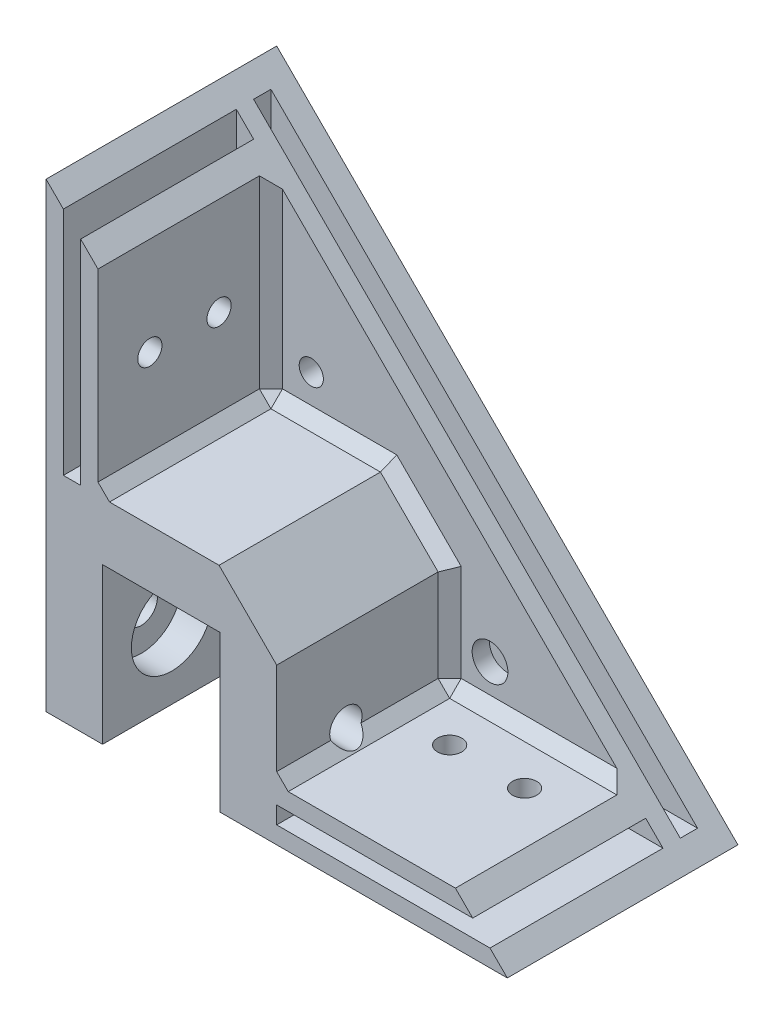
SolidWorks part; units mm, degrees
material "ABS"
ref_plane "Płaszczyzna przednia" through (0, 0, 0) normal (0, 0, 1) x (1, 0, 0)
ref_plane "Płaszczyzna górna" through (0, 0, 0) normal (0, 1, 0) x (1, 0, 0)
ref_plane "Płaszczyzna prawa" through (0, 0, 0) normal (1, 0, 0) x (0, 0, -1)
sketch "Szkic1" plane through (0, 0, 0) normal (0, 0, 1) x (1, 0, 0)
  line L0 (0, 0) -> (80, 0)
  line L1 (0, 0) -> (0, 80)
  line L2 (0, 80) -> (80, 0)
  dimension "D1" = 80
  dimension "D2" = 80
extrude "Dodanie-wyciągnięcie1" add sketch "Szkic1" along normal blind 4
sketch "Szkic2" plane through (0, 0, 4) normal (0, 0, 1) x (1, 0, 0)
  line L0 (3, 77) -> (3, 3)
  line L1 (80, 0) -> (0, 80) construction
  line L2 (3, 3) -> (77, 3)
  line L3 (0, 0) -> (80, 0) construction
  line L4 (0, 80) -> (0, 0) construction
  line L5 (0, 0) -> (80, 0)
  line L6 (0, 80) -> (0, 0)
  line L7 (80, 0) -> (77, 3)
  line L8 (3, 77) -> (0, 80)
  dimension "D1" = 3
  dimension "D2" = 3
extrude "Dodanie-wyciągnięcie2" add sketch "Szkic2" along normal blind 3
sketch "Szkic3" plane through (0, 0, 7) normal (0, 0, 1) x (1, 0, 0)
  line L0 (80, 0) -> (77, 3) construction
  line L1 (0, 0) -> (80, 0) construction
  line L2 (0, 80) -> (0, 0) construction
  line L3 (3, 77) -> (0, 80) construction
  line L4 (77, 3) -> (3, 77) construction
  line L5 (80, 0) -> (77, 3)
  line L6 (0, 0) -> (80, 0)
  line L7 (0, 80) -> (0, 0)
  line L8 (3, 77) -> (0, 80)
  line L9 (77, 3) -> (3, 77)
extrude "Dodanie-wyciągnięcie3" add sketch "Szkic3" along normal blind 3
sketch "Szkic4" plane through (0, 0, 10) normal (0, 0, 1) x (1, 0, 0)
  line L0 (80, 0) -> (30.2, 0)
  line L1 (0, 0) -> (80, 0) construction
  line L2 (77, 3) -> (40, 3)
  line L3 (80, 0) -> (0, 80) construction
  line L4 (40, 3) -> (40, 6)
  line L5 (40, 6) -> (74, 6)
  line L6 (71, 9) -> (40, 9)
  line L7 (0, 0) -> (9.8, 0)
  line L8 (9.8, 0) -> (9.8, 27)
  line L9 (9.8, 27) -> (30.2, 27)
  line L10 (30.2, 27) -> (30.2, 0)
  line L11 (0, 80) -> (0, 0)
  line L12 (40, 9) -> (40, 27)
  line L13 (3, 77) -> (3, 37)
  line L14 (3, 37) -> (6, 37)
  line L15 (6, 37) -> (6, 74)
  line L16 (9, 71) -> (9, 37)
  line L17 (9, 37) -> (30, 37)
  line L18 (30, 37) -> (40, 27)
  line M3 (0, 0) -> (80, 0)
  line M4 (80, 0) -> (0, 80)
  line M5 (0, 80) -> (0, 0)
  dimension "D1" = 49.8
  dimension "D2" = 3
  dimension "D3" = 37
  dimension "D4" = 3
  dimension "D5" = 3
  dimension "D6" = 9.8
  dimension "D7" = 27
  dimension "D8" = 27
  dimension "D9" = 3
  dimension "D10" = 43
  dimension "D11" = 3
  dimension "D12" = 3
  dimension "D13" = 21
extrude "Dodanie-wyciągnięcie4" add sketch "Szkic4" along normal blind 30 contours L18 L17 L16 L15 L14 L13 L8 L9 L10 L2 L4 L5 L6 L12 M4 M5 M3 region at (55.1, 1.1314, 10)
ref_plane "Płaszczyzna1" through (20, 0, 0) normal (1, 0, 0) x (0, 0, -1)
sketch "Szkic5" plane through (20, 0, 0) normal (1, 0, 0) x (0, 0, -1)
  line L0 (-40, 9) -> (-40, 27) construction
  line L1 (-40, 0) -> (0, 0) construction
  circle A0 centre (-28, 12) radius 7
  dimension "D1" = 14
  dimension "D3" = 12
  dimension "D2" = 12
extrude "Wytnij-wyciągnięcie1" cut sketch "Szkic5" against normal blind 15.5 and the other way blind 15.5
sketch "Szkic6" plane through (0, 0, 0) normal (-1, 0, 0) x (0, 0, 1)
  circle A0 centre (28, 12) radius 7 construction
  circle A1 centre (28, 12) radius 7 construction
  circle A2 centre (28, 12) radius 2.8026
extrude "Wytnij-wyciągnięcie2" cut sketch "Szkic6" against normal through all contours A2
chamfer "Sfazowanie1" distance 2 angle 45 7 edges at (40, 9, 25) (9, 37, 25) (9, 54, 10) (19.5, 37, 10) (35, 32, 10) (40, 18, 10) (55.5, 9, 10)
sketch "Szkic7" plane through (0, 0, 10) normal (0, 0, 1) x (1, 0, 0)
  line L0 (30, 37) -> (11, 37) construction
  line L1 (9, 39) -> (9, 71) construction
  line L2 (71, 9) -> (42, 9) construction
  line L3 (40, 11) -> (40, 27) construction
  circle A0 centre (47, 16) radius 3.1
  circle A1 centre (16, 44) radius 2.1
  dimension "D1" = 4.2
  dimension "D6" = 6.2
  dimension "D2" = 7
  dimension "D3" = 7
  dimension "D4" = 7
  dimension "D5" = 7
extrude "Wytnij-wyciągnięcie3" cut sketch "Szkic7" against normal through all
sketch "Szkic8" plane through (0, 9, 0) normal (0, 1, 0) x (1, 0, 0)
  line L0 (42, -10) -> (69, -10) construction
  line L1 (71, -40) -> (71, -12) construction
  line L2 (40, -40) -> (40, -30.6181) construction
  circle A0 centre (49, -19) radius 2.1
  circle A1 centre (62, -19) radius 2.1
  point P11 (40, -35.3091)
  dimension "D4" = 4.2
  dimension "D1" = 9
  dimension "D2" = 9
  dimension "D3" = 9
extrude "Wytnij-wyciągnięcie4" cut sketch "Szkic8" against normal through all
sketch "Szkic9" plane through (9, 0, 0) normal (1, 0, 0) x (0, 0, -1)
  line L0 (-40, 71) -> (-12, 71) construction
  line L1 (-40, 71) -> (-40, 39) construction
  line L2 (-10, 69) -> (-10, 39) construction
  circle A0 centre (-31, 54) radius 2.1
  circle A1 centre (-19, 54) radius 2.1
  dimension "D1" = 4.2
  dimension "D2" = 17
  dimension "D3" = 9
  dimension "D4" = 9
extrude "Wytnij-wyciągnięcie5" cut sketch "Szkic9" against normal through all
